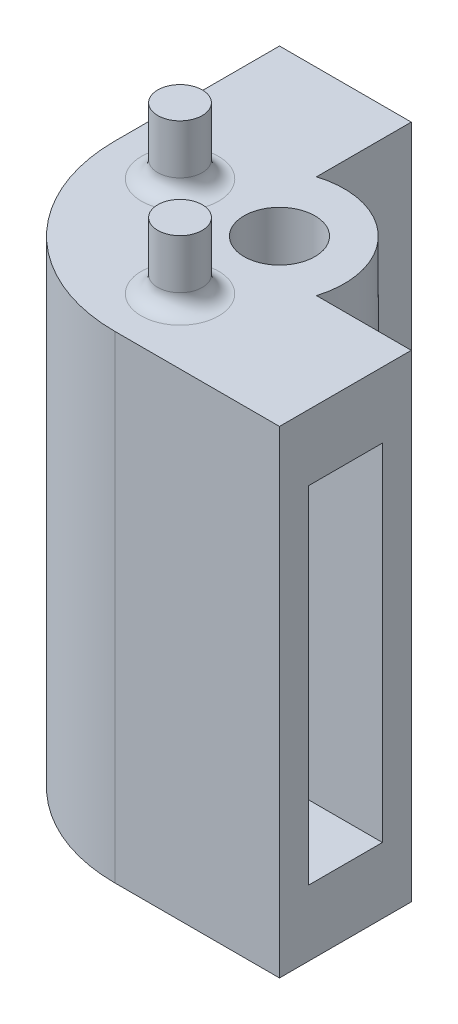
SolidWorks part; units mm, degrees
ref_plane "Front Plane" through (0, 0, 0) normal (0, 0, 1) x (1, 0, 0)
ref_plane "Top Plane" through (0, 0, 0) normal (0, 1, 0) x (1, 0, 0)
ref_plane "Right Plane" through (0, 0, 0) normal (1, 0, 0) x (0, 0, -1)
sketch "Sketch2" plane through (0, 0, 0) normal (0, 1, 0) x (1, 0, 0)
  line L0 (0, 10) -> (0, 20)
  line L1 (0, 20) -> (8, 20)
  line L2 (8, 20) -> (8, 14.2452)
  line L3 (0, 0) -> (22.3158, 22.3158) construction
  line L4 (10, 0) -> (22.3158, 0) construction
  line L5 (18, 8) -> (22.3158, 8) construction
  line L6 (2.9289, 2.9289) -> (9.4645, 9.4645)
  line L7 (9.4645, 9.4645) -> (13, 13)
  arc A0 (2.9289, 2.9289) -> (0, 10) centre (10, 10) cw
  arc A2 (13, 13) -> (8, 14.2452) centre (9.4645, 9.4645) ccw
  point P13 (8, 8)
  dimension "D2" = 10
  dimension "D5" = 10
  dimension "D1" = 8
  dimension "D4" = 20
other "AlignGroup1"
extrude "Boss-Extrude1" add sketch "Sketch2" along normal blind 29
ref_plane "Plane4" through (0, 24, 0) normal (0, 1, 0) x (1, 0, 0)
sketch "Sketch8" [suppressed] plane through (0, 24, 0) normal (0, 1, 0) x (1, 0, 0)
  line L0 (2.9289, 2.9289) -> (13, 13) construction
ref_plane "Plane1" through (0, 0, 0) normal (0.7071, 0, 0.7071) x (0.7071, 0, -0.7071)
mirror "Mirror1" about plane through (0, 0, 0) normal (0.7071, 0, 0.7071) of "Boss-Extrude1"
sketch "Sketch3" plane through (0, 0, -20) normal (0, 0, -1) x (-1, 0, 0)
  line L0 (-4, 0) -> (-4, 4) construction
  line L2 (-8, 0) -> (0, 0) construction
  line L3 (-6.25, 4) -> (-6.25, 25)
  line L4 (-6.25, 4) -> (-1.75, 4)
  line L5 (-6.25, 14.5) -> (-1.75, 14.5) construction
  line L6 (-6.25, 25) -> (-1.75, 25)
  line L7 (-1.75, 4) -> (-1.75, 25)
  dimension "D1" = 4
  dimension "D2" = 4.5
extrude "Cut-Extrude1" cut sketch "Sketch3" against normal blind 6
mirror "Mirror2" about plane through (0, 0, 0) normal (0.7071, 0, 0.7071) of "Cut-Extrude1"
sketch "Sketch5" plane through (0, 29, 0) normal (0, 1, 0) x (1, 0, 0)
  line L0 (2.9289, 2.9289) -> (10, 10) construction
  circle A0 centre (9.9991, 3.9621) radius 1.35
  arc A1 (0, 10) -> (10, 0) centre (10, 10) ccw construction
  circle A2 centre (3.9621, 9.9991) radius 1.35
extrude "Boss-Extrude2" add sketch "Sketch5" along normal blind 4
fillet "Fillet1" radius 1 2 edges at (3.9621, 29, -11.3491) (9.9991, 29, -2.6121)
sketch "Sketch6" plane through (0, 29, 0) normal (0, 1, 0) x (1, 0, 0)
  circle A0 centre (10, 10) radius 2.15
extrude "Cut-Extrude2" cut sketch "Sketch6" against normal through all
ref_plane "Plane2" through (0, 14.5, 0) normal (0, 1, 0) x (1, 0, 0)
sketch "Sketch9" plane through (0, 24, 0) normal (0, 1, 0) x (1, 0, 0)
  line L0 (8.9391, 13.9595) -> (13.429, 18.4495)
  line L1 (7.1014, 7.1014) -> (11.0609, 6.0405)
  line L2 (11.0609, 6.0405) -> (13.9595, 8.9391)
  line L3 (13.9595, 8.9391) -> (18.4293, 13.7623)
  line L5 (8.9391, 13.9595) -> (6.0405, 11.0609)
  line L6 (6.0405, 11.0609) -> (7.1014, 7.1014)
  line L9 (13.429, 18.4495) -> (18.4293, 13.7623)
  line L11 (10.9188, 13.429) -> (8.9391, 13.9595) [skipped]
  line L12 (13.9595, 8.9391) -> (13.9481, 8.9817) [skipped]
  circle A0 centre (10, 10) radius 3.55 construction
  dimension "D1" = 7.1
extrude "Cut-Extrude3" cut sketch "Sketch9" against normal blind 3.5 contours L9 L3 L2 L1 L6 L5 L0
mirror "Mirror4" about plane through (0, 14.5, 0) normal (0, 1, 0) of "Cut-Extrude3"
